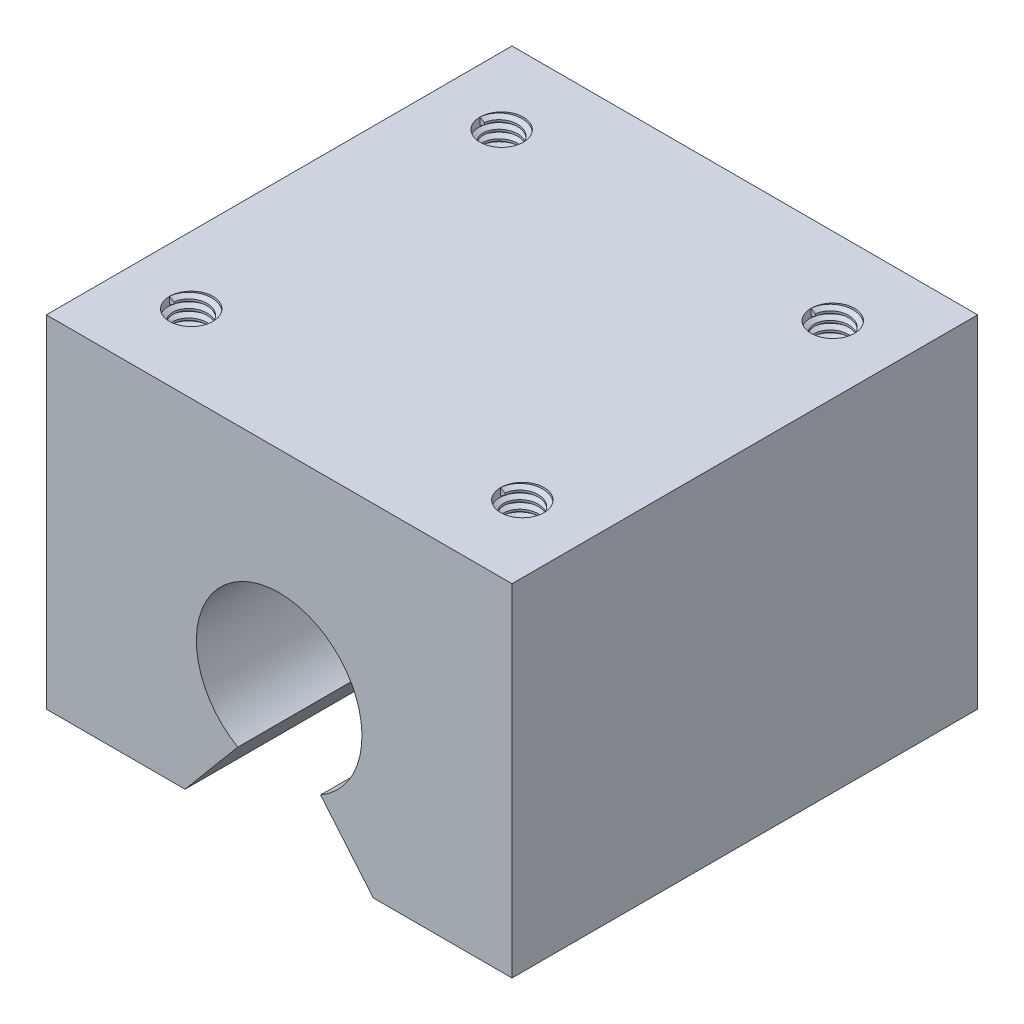
SolidWorks part; units mm, degrees
ref_plane "Front Plane" through (0, 0, 0) normal (0, 0, 1) x (1, 0, 0)
ref_plane "Top Plane" through (0, 0, 0) normal (0, 1, 0) x (1, 0, 0)
ref_plane "Right Plane" through (0, 0, 0) normal (1, 0, 0) x (0, 0, -1)
sketch "Sketch1" plane through (0, 0, 0) normal (0, 0, 1) x (1, 0, 0)
  line L0 (32.069, 0) -> (32.069, 33)
  line L1 (32.069, 33) -> (-12.931, 33)
  line L2 (-12.931, 33) -> (-12.931, 0)
  line L3 (-12.931, 0) -> (0.4741, 0)
  line L4 (0.4741, 0) -> (5.569, 6.0718)
  line L5 (32.069, 0) -> (18.6638, 0)
  line L6 (18.6638, 0) -> (13.569, 6.0718)
  arc A0 (5.569, 6.0718) -> (13.569, 6.0718) centre (9.569, 13) cw
  dimension "D3" = 8
  dimension "D1" = 45
  dimension "D2" = 33
  dimension "D4" = 80
  dimension "D5" = 8
  dimension "D6" = 20
extrude "Boss-Extrude1" add sketch "Sketch1" along normal blind 45
sketch "Sketch2" plane through (0, 33, 0) normal (0, 1, 0) x (1, 0, 0)
  line L0 (-12.931, -45) -> (-12.931, 0) construction
  line L5 (32.069, 0) -> (-12.931, 0) construction
  point P0 (-6.431, -7.5)
  point P1 (25.569, -7.5)
  point P2 (25.569, -37.5)
  point P3 (-6.431, -37.5)
  dimension "D1" = 32
  dimension "D2" = 6.5
  dimension "D3" = 30
  dimension "D4" = 7.5
hole_wizard "Tap Drill for M5x0.8 Tap1" positions "Sketch3" profile "Sketch5" hole size "M5x0.8" standard "ANSI Metric"
sketch "Sketch3" plane through (0, 33, 0) normal (0, 1, 0) x (1, 0, 0)
  point P0 (-6.431, -7.5)
  point P3 (25.569, -7.5)
  point P6 (25.569, -37.5)
  point P9 (-6.431, -37.5)
sketch "Sketch5" plane through (-6.431, 33, 7.5) normal (1, 0, 0) x (0, 0, 1)
  line L0 (0, 0) -> (0, 13.2618)
  line L1 (0, 13.2618) -> (2.1, 12)
  line L2 (2.1, 12) -> (2.1, 0)
  line L5 (2.1, 0) -> (0, 0)
  line L10 (0, 13.2618) -> (-2.1, 12) construction
  line L11 (0, -6.35) -> (0, 107.95) construction
  dimension "Hole Dia." = 4.2
  dimension "Hole Depth" = 12
  dimension "Drill Angle" = 118
thread "Thread1" pitch 0.8 method extrude profile "Thread Profile1" start angle 0, offset 0, length 0, pitch 0.8, diameter 4.2
ref_plane "Plane1" through (23.469, 33, 37.5) normal (0, 0, 1) x (-1, 0, 0)
sketch "Thread Profile1" plane through (23.469, 33, 37.5) normal (0, 0, 1) x (-1, 0, 0)
  line L0 (0, 0) -> (0, 0.8) construction
  line L11 (0, 0) -> (0, 0.7)
  line L12 (0, 0.7) -> (-0.433, 0.45)
  line L13 (-0.433, 0.45) -> (-0.433, 0.25)
  line L15 (-0.433, 0.25) -> (0, 0)
  line L17 (-0.433, 0.35) -> (0, 0.35) construction
  point P2 (0, 0)
  dimension "Pitch" = 0.8
  dimension "Profile_Angle" = 60
  dimension "Profile_Land" = 0.2
  dimension "Profile_Height" = 0.433
thread "Thread2" pitch 0.8 method extrude profile "Thread Profile2" start angle 0, offset 0, length 0, pitch 0.8, diameter 4.2
ref_plane "Plane2" through (-8.531, 33, 37.5) normal (0, 0, 1) x (-1, 0, 0)
sketch "Thread Profile2" plane through (-8.531, 33, 37.5) normal (0, 0, 1) x (-1, 0, 0)
  line L0 (0, 0) -> (0, 0.8) construction
  line L11 (0, 0) -> (0, 0.7)
  line L12 (0, 0.7) -> (-0.433, 0.45)
  line L13 (-0.433, 0.45) -> (-0.433, 0.25)
  line L15 (-0.433, 0.25) -> (0, 0)
  line L17 (-0.433, 0.35) -> (0, 0.35) construction
  point P2 (0, 0)
  dimension "Pitch" = 0.8
  dimension "Profile_Angle" = 60
  dimension "Profile_Land" = 0.2
  dimension "Profile_Height" = 0.433
thread "Thread3" pitch 0.8 method extrude profile "Thread Profile3" start angle 0, offset 0, length 0, pitch 0.8, diameter 4.2
ref_plane "Plane3" through (23.469, 33, 7.5) normal (0, 0, 1) x (-1, 0, 0)
sketch "Thread Profile3" plane through (23.469, 33, 7.5) normal (0, 0, 1) x (-1, 0, 0)
  line L0 (0, 0) -> (0, 0.8) construction
  line L11 (0, 0) -> (0, 0.7)
  line L12 (0, 0.7) -> (-0.433, 0.45)
  line L13 (-0.433, 0.45) -> (-0.433, 0.25)
  line L15 (-0.433, 0.25) -> (0, 0)
  line L17 (-0.433, 0.35) -> (0, 0.35) construction
  point P2 (0, 0)
  dimension "Pitch" = 0.8
  dimension "Profile_Angle" = 60
  dimension "Profile_Land" = 0.2
  dimension "Profile_Height" = 0.433
thread "Thread4" pitch 0.8 method extrude profile "Thread Profile4" start angle 0, offset 0, length 0, pitch 0.8, diameter 4.2
ref_plane "Plane4" through (-8.531, 33, 7.5) normal (0, 0, 1) x (-1, 0, 0)
sketch "Thread Profile4" plane through (-8.531, 33, 7.5) normal (0, 0, 1) x (-1, 0, 0)
  line L0 (0, 0) -> (0, 0.8) construction
  line L11 (0, 0) -> (0, 0.7)
  line L12 (0, 0.7) -> (-0.433, 0.45)
  line L13 (-0.433, 0.45) -> (-0.433, 0.25)
  line L15 (-0.433, 0.25) -> (0, 0)
  line L17 (-0.433, 0.35) -> (0, 0.35) construction
  point P2 (0, 0)
  dimension "Pitch" = 0.8
  dimension "Profile_Angle" = 60
  dimension "Profile_Land" = 0.2
  dimension "Profile_Height" = 0.433
